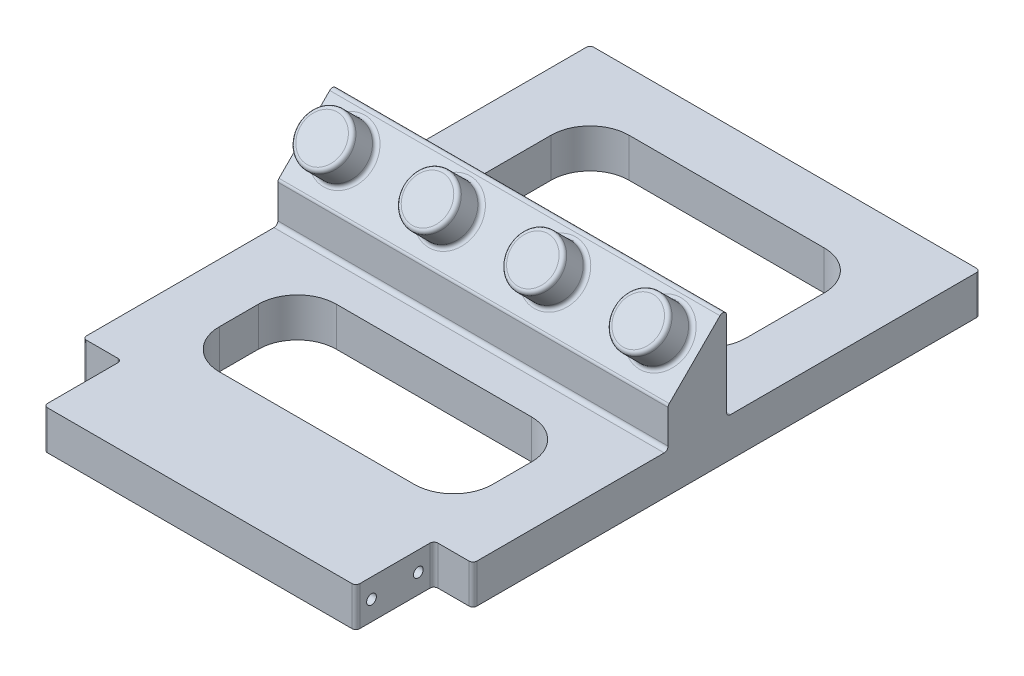
SolidWorks part; units mm, degrees
ref_plane "前视基准面" through (0, 0, 0) normal (0, 0, 1) x (1, 0, 0)
ref_plane "上视基准面" through (0, 0, 0) normal (0, 1, 0) x (1, 0, 0)
ref_plane "右视基准面" through (0, 0, 0) normal (1, 0, 0) x (0, 0, -1)
sketch "草图1" plane through (0, 0, 0) normal (0, 1, 0) x (1, 0, 0)
  line L1 (-50, -75) -> (50, -75)
  line L2 (-50, -75) -> (-50, 75)
  line L3 (-50, 75) -> (50, 75)
  line L4 (50, -75) -> (50, 75)
  line L5 (-50, -75) -> (50, 75) construction
  line L6 (-50, 75) -> (50, -75) construction
  point P0 (0, 0)
  dimension "D1" = 100
  dimension "D2" = 150
extrude "凸台-拉伸1" add sketch "草图1" along normal mid plane 10
sketch "草图6" plane through (50, 0, 0) normal (1, 0, 0) x (0, 0, -1)
  line L0 (-75, -5) -> (75, -5) construction
  line L1 (-55, -5) -> (-75, -5)
  line L2 (-55, -5) -> (-55, 5)
  line L3 (-55, 5) -> (-75, 5)
  line L4 (-75, -5) -> (-75, 5)
  line L5 (-55, -5) -> (-75, 5) construction
  line L6 (-55, 5) -> (-75, -5) construction
  point P0 (-65, 0)
  point P6 (-54.3449, 0)
  dimension "D1" = 20
extrude "切除-拉伸2" cut sketch "草图6" against normal blind 10
sketch "草图8" plane through (40, 0, 0) normal (1, 0, 0) x (0, 0, -1)
  line L0 (-55, -5) -> (-55, 5) construction
  line L1 (-55, -5) -> (-75, -5) construction
  line L2 (-55, -5) -> (-55, 5) construction
  line L3 (-55, 5) -> (-75, 5) construction
  line L4 (-75, -5) -> (-75, 5) construction
  line L5 (-55, -5) -> (-75, 5) construction
  line L6 (-55, 5) -> (-75, -5) construction
  line L7 (-55, -5) -> (-55, 5) construction
  line L8 (-55, -5) -> (75, -5) construction
  line L9 (-59, 0) -> (-71, 0) construction
  circle A0 centre (-71, 0) radius 1.25
  circle A1 centre (-59, 0) radius 1.25
  point P0 (-65, 0)
  point P16 (-58.9241, 0)
  point P19 (-65, 0)
  dimension "D2" = 2.5
  dimension "D1" = 12
extrude "切除-拉伸3" cut sketch "草图8" against normal blind 15
mirror "镜向1" about plane through (0, 0, 0) normal (1, 0, 0) of "切除-拉伸2", "切除-拉伸3"
sketch "草图9" plane through (50, 0, 0) normal (1, 0, 0) x (0, 0, -1)
  line L0 (-55, 5) -> (75, 5) construction
  line L1 (-5, 15) -> (10, 15) construction
  line L2 (-5, 15) -> (-5, 5)
  line L3 (-5, 5) -> (10, 5)
  line L4 (10, 15) -> (10, 5)
  line L5 (-5, 15) -> (10, 5) construction
  line L6 (-5, 5) -> (10, 15) construction
  line L7 (-5, 15) -> (10, 30)
  line L8 (10, 30) -> (10, 15)
  line L9 (-75, 5) -> (-75, -5) construction
  point P0 (2.5, 10)
  point P7 (-10.2523, 55.73)
  point P9 (-29.8901, 5)
  dimension "D1" = 45
  dimension "D2" = 15
  dimension "D3" = 10
  dimension "D4" = 70
extrude "凸台-拉伸3" add sketch "草图9" against normal up to surface (100 mm away) up to face at (-50, 0, -10)
sketch "草图10" plane through (0, 10, 10) normal (0, 0.7071, 0.7071) x (1, 0, 0)
  line L0 (-40.5, 17.6777) -> (40.5, 17.6777) construction
  line L2 (-50, 28.2843) -> (50, 7.0711) construction
  circle A0 centre (40.5, 17.6777) radius 6.5
  circle A1 centre (-40.5, 17.6777) radius 6.5
  circle A2 centre (-13.5, 17.6777) radius 6.5
  circle A3 centre (13.5, 17.6777) radius 6.5
  point P3 (0, 17.6777)
  dimension "D1" = 13
  dimension "D2" = 81
  dimension "D3" = 27
  dimension "D4" = 27
extrude "凸台-拉伸4" add sketch "草图10" along normal blind 8
fillet "圆角1" radius 1 12 edges at (-40.5, 17.9038, 2.0962) (-40.5, 23.5607, 7.753) (-13.5, 17.9038, 2.0962) (-13.5, 23.5607, 7.753) (13.5, 17.9038, 2.0962) (13.5, 23.5607, 7.753) (40.5, 17.9038, 2.0962) (40.5, 23.5607, 7.753) (0, 5, 5) (0, 5, -10) (0, 15, 5) (0, 30, -10)
fillet "圆角2" radius 1 8 edges at (50, 0, -75) (-50, 0, -75) (50, 0, 55) (40, 0, 55) (40, 0, 75) (-40, 0, 75) (-40, 0, 55) (-50, 0, 55)
sketch "草图11" plane through (0, 5, 0) normal (0, 1, 0) x (1, 0, 0)
  line L0 (49, 75) -> (-49, 75) construction
  line L1 (-35, 20) -> (35, 20)
  line L2 (-35, 20) -> (-35, 60)
  line L3 (-35, 60) -> (35, 60)
  line L4 (35, 20) -> (35, 60)
  line L5 (-35, 20) -> (35, 60) construction
  line L6 (-35, 60) -> (35, 20) construction
  line L7 (-35, -15) -> (35, -15)
  line L8 (-35, -15) -> (-35, -45)
  line L9 (-35, -45) -> (35, -45)
  line L10 (35, -15) -> (35, -45)
  line L11 (-35, -15) -> (35, -45) construction
  line L12 (-35, -45) -> (35, -15) construction
  line L13 (-41, -55) -> (-49, -55) construction
  point P0 (0, 40)
  point P5 (0, -30)
  point P12 (0, 0)
  point P14 (0, 0)
  dimension "D1" = 15
  dimension "D2" = 40
  dimension "D3" = 70
  dimension "D4" = 10
  dimension "D5" = 30
extrude "切除-拉伸4" cut sketch "草图11" against normal through all
fillet "圆角3" radius 10 8 edges at (-35, 0, 15) (35, 0, 15) (-35, 0, 45) (35, 0, 45) (35, 0, -20) (-35, 0, -20) (35, 0, -60) (-35, 0, -60)
